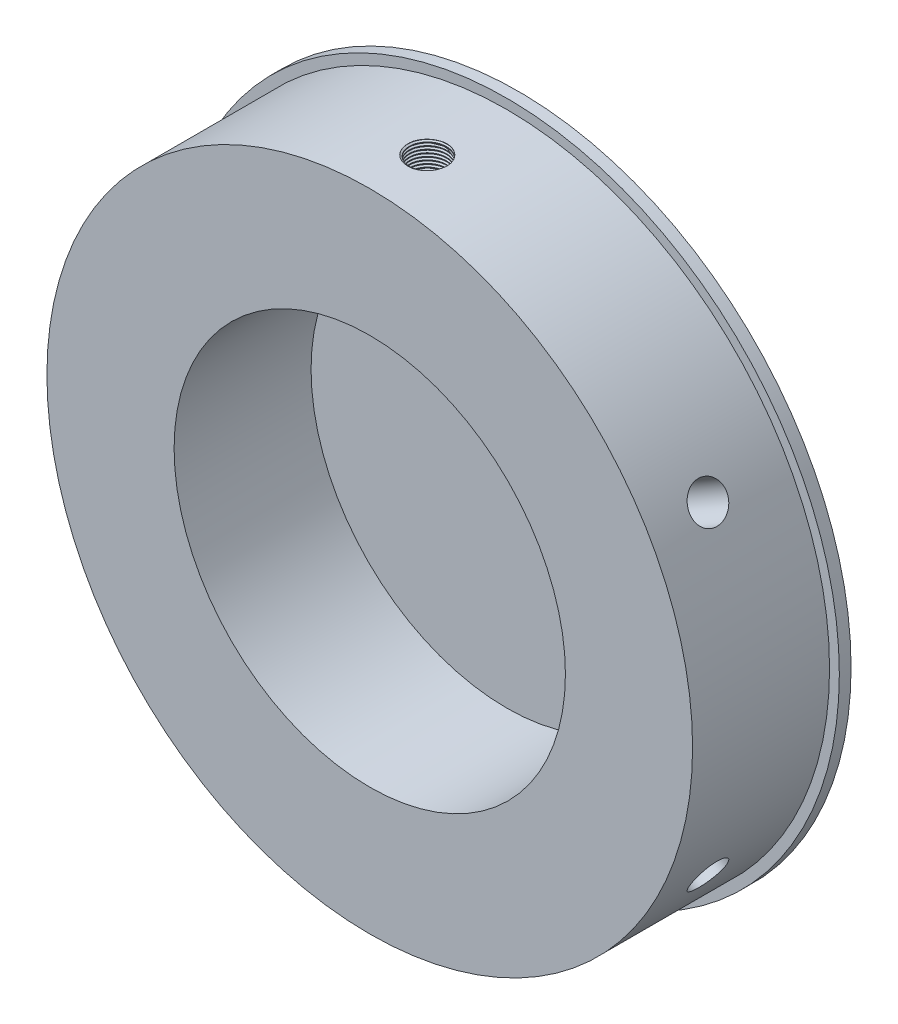
SolidWorks part; units mm, degrees
ref_plane "Front Plane" through (0, 0, 0) normal (0, 0, 1) x (1, 0, 0)
ref_plane "Top Plane" through (0, 0, 0) normal (0, 1, 0) x (1, 0, 0)
ref_plane "Right Plane" through (0, 0, 0) normal (1, 0, 0) x (0, 0, -1)
sketch "Sketch1" plane through (0, 0, 0) normal (0, 0, 1) x (1, 0, 0)
  circle A0 centre (0, 0) radius 85
ref_plane "Plane1" through (0, 0, 3) normal (0, 0, 1) x (1, 0, 0)
sketch "Sketch2" plane through (0, 0, 3) normal (0, 0, 1) x (1, 0, 0)
  circle A0 centre (0, 0) radius 82.5
extrude "Boss-Extrude2" add sketch "Sketch1" along normal blind 3 contours A0
extrude "Boss-Extrude3" add sketch "Sketch2" along normal blind 35 contours A0
ref_plane "Plane2" through (0, 0, 38) normal (0, 0, 1) x (1, 0, 0)
sketch "Sketch3" plane through (0, 0, 38) normal (0, 0, 1) x (1, 0, 0)
  circle A0 centre (0, 0) radius 50
extrude "Cut-Extrude1" cut sketch "Sketch3" against normal blind 35
ref_plane "Plane3" through (0, 82.5, 0) normal (0, -1, 0) x (-1, 0, 0)
sketch "Sketch9" plane through (0, 82.5, 0) normal (0, -1, 0) x (-1, 0, 0)
  line L0 (0, -3) -> (0, -23)
  line L1 (-93.5, -3) -> (93.5, -3) construction
  circle A0 centre (0, -23) radius 4.7625
extrude "Cut-Extrude9" cut sketch "Sketch9" along normal blind 19.05 contours A0
pattern_circular "CirPattern1" count 6 over 360 about axis through (0, 0, 38) along (0, 0, -1) of "Cut-Extrude9"
ref_plane "Plane4" through (0, 85, 0) normal (0, 1, 0) x (1, 0, 0)
ref_plane "Plane5" through (0, -85, 0) normal (0, -1, 0) x (-1, 0, 0)
ref_plane "Plane6" through (85, 0, 0) normal (1, 0, 0) x (0, 0, -1)
ref_plane "Plane7" through (-85, 0, 0) normal (-1, 0, 0) x (0, 0, 1)
thread "Thread1" pitch 0.7937 method cut profile "Thread Profile1" start angle 0, offset 0, length 19.05, pitch 0.7937, diameter 9.525
ref_plane "Plane8" through (4.7625, -85, 23) normal (0, 0, 1) x (1, 0, 0)
sketch "Thread Profile1" plane through (4.7625, -85, 23) normal (0, 0, 1) x (1, 0, 0)
  line L0 (0, 0) -> (0, 0.7937) construction
  line L1 (0, 0) -> (0.4296, 0.248)
  line L2 (0.4296, 0.248) -> (0.4296, 0.3473)
  line L3 (0.4296, 0.3473) -> (0, 0.5953)
  line L4 (0.4296, 0.2977) -> (0, 0.2977) construction
  line L11 (0, 0) -> (0, 0.5953)
  point P2 (0, 0)
  dimension "Pitch" = 0.7937
  dimension "Profile_Angle" = 60
  dimension "Profile_Land" = 0.0992
  dimension "Profile_Height" = 0.4296
thread "Thread2" pitch 0.7937 method cut profile "Thread Profile2" start angle 0, offset 0, length 19.05, pitch 0.7937, diameter 9.525
ref_plane "Plane9" through (-4.7625, 85, 23) normal (0, 0, 1) x (-1, 0, 0)
sketch "Thread Profile2" plane through (-4.7625, 85, 23) normal (0, 0, 1) x (-1, 0, 0)
  line L0 (0, 0) -> (0, 0.7937) construction
  line L1 (0, 0) -> (0.4296, 0.248)
  line L2 (0.4296, 0.248) -> (0.4296, 0.3473)
  line L3 (0.4296, 0.3473) -> (0, 0.5953)
  line L4 (0.4296, 0.2977) -> (0, 0.2977) construction
  line L11 (0, 0) -> (0, 0.5953)
  point P2 (0, 0)
  dimension "Pitch" = 0.7937
  dimension "Profile_Angle" = 60
  dimension "Profile_Land" = 0.0992
  dimension "Profile_Height" = 0.4296
